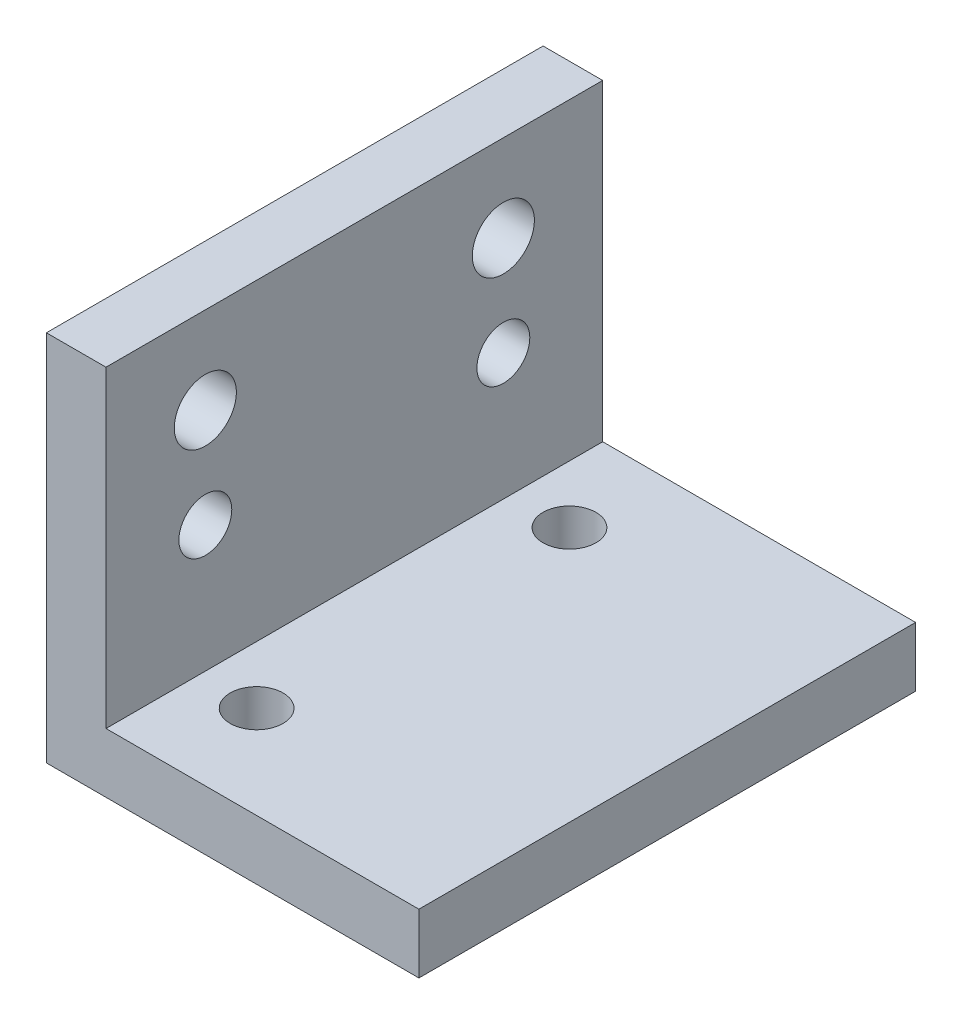
SolidWorks part; units mm, degrees
ref_plane "Front" through (0, 0, 0) normal (0, 0, 1) x (1, 0, 0)
ref_plane "Top" through (0, 0, 0) normal (0, 1, 0) x (1, 0, 0)
ref_plane "Right" through (0, 0, 0) normal (1, 0, 0) x (0, 0, -1)
ref_axis "side-side" through (80.9, 0, 0) along (-1, 0, 0)
ref_axis "up-down" through (0, 50, 0) along (0, -1, 0)
ref_axis "front-back" through (0, 0, -80.9) along (0, 0, 1)
sketch "Sketch1" plane through (0, 0, 0) normal (0, 0, 1) x (1, 0, 0)
  line L1 (0, 0) -> (19.05, 0)
  line L2 (0, 0) -> (0, 19.05)
  line L3 (0, 19.05) -> (3.048, 19.05)
  line L4 (19.05, 0) -> (19.05, 3.048)
  line L7 (19.05, 3.048) -> (3.048, 3.048)
  line L8 (3.048, 19.05) -> (3.048, 3.048)
  dimension "D1" = 19.05
  dimension "D2" = 3.048
extrude "Boss-Extrude1" add sketch "Sketch1" along normal blind 25.4
sketch "Sketch2" plane through (3.048, 0, 0) normal (1, 0, 0) x (0, 0, -1)
  line L0 (-25.4, 19.05) -> (0, 0) construction
  line L1 (-20.32, 9.525) -> (-5.08, 9.525) construction
  line L2 (-25.4, 3.048) -> (-25.4, 19.05) construction
  point P6 (-12.7, 9.525)
  dimension "D1" = 5.08
hole_wizard "#6-32 Tapped Hole1" positions "Sketch4" profile "Sketch3" tap size "#6-32" standard "ANSI Inch" end condition through all
sketch "Sketch4" plane through (3.048, 0, 0) normal (1, 0, 0) x (0, 0, -1)
  point P0 (-20.32, 9.525)
  point P3 (-5.08, 9.525)
sketch "Sketch3" plane through (3.048, 9.525, 20.32) normal (0, 1, 0) x (0, 0, -1)
  line L0 (0, 0) -> (0, 3.048)
  line L1 (0, 3.048) -> (1.3525, 3.048)
  line L2 (1.3525, 3.048) -> (1.3525, 0)
  line L5 (1.3525, 0) -> (0, 0)
  line L11 (0, -6.35) -> (0, 107.95) construction
  dimension "Thread Major Dia." = 2.7051
  dimension "Thru Tap Drill Depth" = 3.048
hole_wizard "#6-32 Tapped Hole2" positions "Sketch6" profile "Sketch5" tap size "#6-32" standard "ANSI Inch" end condition through all
sketch "Sketch6" plane through (0, 3.048, 0) normal (0, 1, 0) x (1, 0, 0)
  point P0 (6, -20.65)
  point P3 (6, -4.65)
sketch "Sketch5" plane through (6, 3.048, 20.65) normal (1, 0, 0) x (0, 0, 1)
  line L0 (0, 0) -> (0, 3.048)
  line L1 (0, 3.048) -> (1.3525, 3.048)
  line L2 (1.3525, 3.048) -> (1.3525, 0)
  line L5 (1.3525, 0) -> (0, 0)
  line L11 (0, -6.35) -> (0, 107.95) construction
  dimension "Thread Major Dia." = 2.7051
  dimension "Thru Tap Drill Depth" = 3.048
sketch "Sketch7" plane through (3.048, 0, 0) normal (1, 0, 0) x (0, 0, -1)
  circle A0 centre (-20.32, 14.605) radius 1.5875
  circle A1 centre (-5.08, 14.605) radius 1.5875
  dimension "D2" = 3.175
  dimension "D1" = 5.08
extrude "Cut-Extrude1" cut sketch "Sketch7" against normal through all
